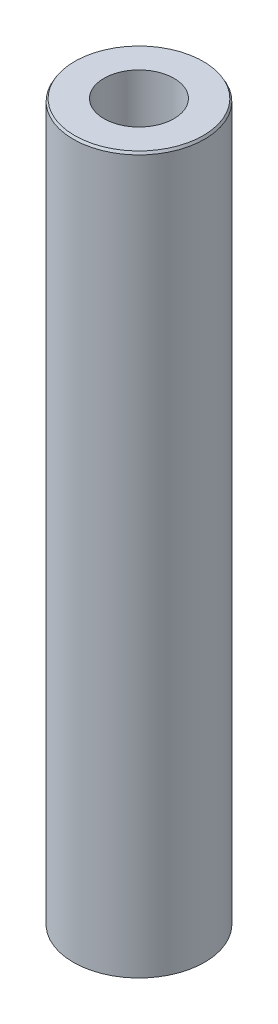
SolidWorks part; units mm, degrees
ref_plane "Front Plane" through (0, 0, 0) normal (0, 0, 1) x (1, 0, 0)
ref_plane "Top Plane" through (0, 0, 0) normal (0, 1, 0) x (1, 0, 0)
ref_plane "Right Plane" through (0, 0, 0) normal (1, 0, 0) x (0, 0, -1)
sketch "Sketch1" plane through (0, 0, 0) normal (0, 1, 0) x (1, 0, 0)
  circle A0 centre (0, 0) radius 55
  dimension "SHAFT_OD" = 110
extrude "Boss-Extrude1" add sketch "Sketch1" along normal blind 600
sketch "Sketch2" plane through (0, 0, 0) normal (0, 1, 0) x (1, 0, 0)
  circle A0 centre (0, 0) radius 29.3117
  dimension "BORE_D" = 58.6233
extrude "Cut-Extrude1" cut sketch "Sketch2" along normal through all
chamfer "Chamfer1" distance 2.0431 angle 30 2 edges at (0, 600, 55) (0, 0, 55) first distance on face at (0, 600, 55) first distance on face at (0, 0, 29.3117)
